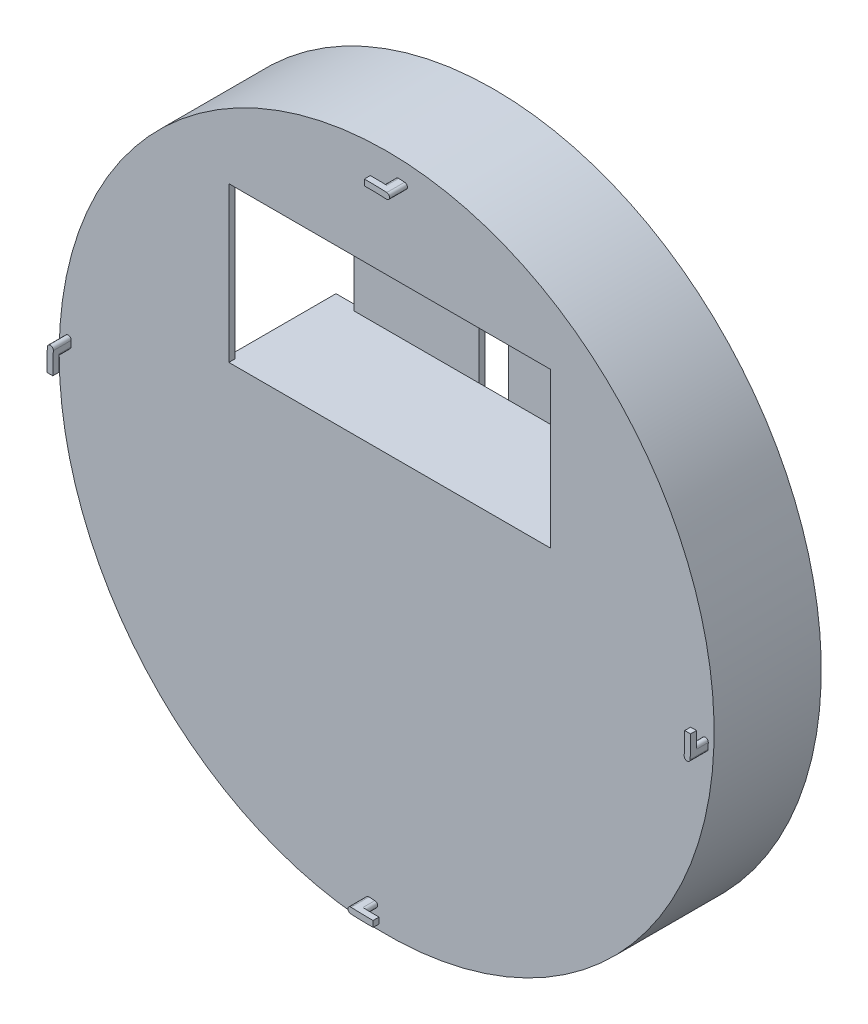
SolidWorks part; units mm, degrees
ref_plane "Plan de face" through (0, 0, 0) normal (0, 0, 1) x (1, 0, 0)
ref_plane "Plan de dessus" through (0, 0, 0) normal (0, 1, 0) x (1, 0, 0)
ref_plane "Plan de droite" through (0, 0, 0) normal (1, 0, 0) x (0, 0, -1)
sketch "Esquisse1" plane through (0, 0, 0) normal (0, 0, 1) x (1, 0, 0)
  ellipse E0 centre (0, 0) end of major axis (0, 57) minor radius 55
  dimension "D1" = 55
  dimension "D2" = 57
extrude "Boss.-Extru.1" add sketch "Esquisse1" along normal blind 18
sketch "Esquisse2" plane through (0, 0, 0) normal (0, 0, -1) x (-1, 0, 0)
  circle A0 centre (0, 0) radius 50
  dimension "D1" = 100
extrude "Enlèv. mat.-Extru.1" cut sketch "Esquisse2" against normal blind 17
sketch "Esquisse3" plane through (0, 0, 17) normal (0, 0, -1) x (-1, 0, 0)
  line L1 (-28.5, 40) -> (27.5, 40)
  line L2 (-28.5, 40) -> (-28.5, 12)
  line L3 (-28.5, 12) -> (27.5, 12)
  line L4 (27.5, 40) -> (27.5, 12)
  line L5 (-28.5, 40) -> (27.5, 12) construction
  line L6 (-28.5, 12) -> (27.5, 40) construction
  circle A0 centre (0, 0) radius 50 construction
  circle A1 centre (0, 0) radius 50 construction
  point P0 (-0.5, 26)
  dimension "D3" = 40
  dimension "D4" = 27.5
  dimension "D1" = 56
  dimension "D2" = 28
extrude "Boss.-Extru.2" add sketch "Esquisse3" along normal blind 18
sketch "Esquisse4" plane through (0, 0, 18) normal (0, 0, 1) x (1, 0, 0)
  line L0 (10.45, 0) -> (-10.45, 0) construction
  line L1 (-26.5, 39) -> (27.5, 39)
  line L2 (-26.5, 39) -> (-26.5, 13)
  line L3 (-26.5, 13) -> (27.5, 13)
  line L4 (27.5, 39) -> (27.5, 13)
  line L5 (-26.5, 39) -> (27.5, 13) construction
  line L6 (-26.5, 13) -> (27.5, 39) construction
  line L7 (0, -10.45) -> (0, 10.45) construction
  point P0 (0.5, 26)
  dimension "D1" = 54
  dimension "D2" = 26
  dimension "D3" = 39
  dimension "D4" = 27.5
extrude "Enlèv. mat.-Extru.2" cut sketch "Esquisse4" against normal blind 18
sketch "Esquisse5" plane through (0, 0, -1) normal (0, 0, -1) x (-1, 0, 0)
  line L0 (-2.5, 12) -> (2.5, 12)
  line L1 (-2.5, 12) -> (-2.5, 40)
  line L2 (2.5, 12) -> (2.5, 40)
  line L3 (-2.5, 40) -> (2.5, 40)
  line L4 (-28.5, 12) -> (27.5, 12) construction
  line L5 (-28.5, 12) -> (27.5, 12) construction
  line L7 (0, 10.45) -> (0, -10.45) construction
  dimension "D1" = 5
  dimension "D2" = 2.5
  dimension "D3" = 28
extrude "Enlèv. mat.-Extru.3" cut sketch "Esquisse5" against normal blind 1
sketch "Esquisse7" plane through (2.5, 0, 0) normal (-1, 0, 0) x (0, 0, 1)
  line L0 (-1, 40) -> (-1, 12)
  line L1 (-1, 12) -> (3, 40)
  line L2 (3, 40) -> (-1, 40)
  dimension "D1" = 4
extrude "Enlèv. mat.-Extru.4" cut sketch "Esquisse7" along normal blind 5
sketch "Esquisse8" plane through (0, 0, 17) normal (0, 0, -1) x (-1, 0, 0)
  line L0 (0, 40) -> (0, 50) construction
  line L1 (2.5, 40) -> (-2.5, 40) construction
  line L2 (-5.5, 46) -> (5.5, 46) construction
  line L3 (27.5, 40) -> (-28.5, 40) construction
  line L8 (-5.5, 46) -> (-5.5, 40)
  line L9 (-5.5, 46) -> (-2, 46)
  line L10 (-2, 46) -> (-2, 45)
  line L11 (-2, 45) -> (-4.5, 45)
  line L12 (-4.5, 45) -> (-4.5, 41)
  line L13 (-4.5, 41) -> (-2, 41)
  line L14 (-2, 41) -> (-2, 40)
  line L15 (-2, 40) -> (-5.5, 40)
  line L16 (5.5, 46) -> (5.5, 40)
  line L17 (2, 40) -> (5.5, 40)
  line L18 (2, 41) -> (2, 40)
  line L19 (4.5, 41) -> (2, 41)
  line L20 (4.5, 45) -> (4.5, 41)
  line L21 (2, 45) -> (4.5, 45)
  line L22 (2, 46) -> (2, 45)
  line L23 (5.5, 46) -> (2, 46)
  circle A0 centre (0, 0) radius 50 construction
  point P10 (0, 46)
  dimension "D1" = 11
  dimension "D2" = 6
  dimension "D3" = 6
  dimension "D4" = 3.5
  dimension "D5" = 3.5
  dimension "D6" = 1
  dimension "D7" = 4
  dimension "D8" = 1
extrude "Boss.-Extru.3" add sketch "Esquisse8" along normal blind 10
sketch "Esquisse9" plane through (0, 0, -1) normal (0, 0, -1) x (-1, 0, 0)
  line L0 (27.5, 12) -> (27.5, 40) construction
  line L7 (27.5, 13) -> (27.5, 39)
  line L8 (27.5, 13) -> (23.5, 13)
  line L9 (27.5, 39) -> (23.5, 39)
  line L10 (23.5, 13) -> (23.5, 39)
  point P0 (27.5, 26)
  dimension "D3" = 4
  dimension "D4" = 26
extrude "Enlèv. mat.-Extru.5" cut sketch "Esquisse9" against normal blind 18
sketch "Esquisse10" plane through (0, 0, -1) normal (0, 0, -1) x (-1, 0, 0)
  line L0 (-5.5, 40) -> (-28.5, 40) construction
  line L1 (-2.5, 40) -> (-2.5, 12) construction
  line L2 (27.5, 40) -> (2.5, 40) construction
  line L3 (2.5, 12) -> (2.5, 40) construction
  circle A0 centre (-9.5, 26) radius 3
  circle A1 centre (9.5, 26) radius 3
  dimension "D1" = 14
  dimension "D2" = 7
  dimension "D3" = 14
  dimension "D4" = 7
  dimension "D5" = 6
  dimension "D6" = 6
extrude "Boss.-Extru.4" add sketch "Esquisse10" along normal blind 15
sketch "Esquisse11" plane through (0, 0, 18) normal (0, 0, 1) x (1, 0, 0)
  arc A0 (-53.521, 2) -> (-53.4743, 3) centre (0, 0) cw construction
  arc A1 (-53.9735, 3.028) -> (-54.0207, 2.0187) centre (0, 0) ccw
  arc A2 (-52.9751, 2.972) -> (-53.0214, 1.9813) centre (0, 0) ccw
  arc A3 (-52.9751, 2.972) -> (-53.9735, 3.028) centre (-53.4743, 3) ccw
  arc A4 (-54.0207, 2.0187) -> (-53.0214, 1.9813) centre (-53.521, 2) ccw
  arc A5 (2, 53.521) -> (3, 53.4743) centre (0, 0) cw construction
  arc A6 (3.028, 53.9735) -> (2.0187, 54.0207) centre (0, 0) ccw
  arc A7 (2.972, 52.9751) -> (1.9813, 53.0214) centre (0, 0) ccw
  arc A8 (2.972, 52.9751) -> (3.028, 53.9735) centre (3, 53.4743) ccw
  arc A9 (2.0187, 54.0207) -> (1.9813, 53.0214) centre (2, 53.521) ccw
  arc A10 (53.521, -2) -> (53.4743, -3) centre (0, 0) cw construction
  arc A11 (53.9735, -3.028) -> (54.0207, -2.0187) centre (0, 0) ccw
  arc A12 (52.9751, -2.972) -> (53.0214, -1.9813) centre (0, 0) ccw
  arc A13 (52.9751, -2.972) -> (53.9735, -3.028) centre (53.4743, -3) ccw
  arc A14 (54.0207, -2.0187) -> (53.0214, -1.9813) centre (53.521, -2) ccw
  arc A15 (-2, -53.521) -> (-3, -53.4743) centre (0, 0) cw construction
  arc A16 (-3.028, -53.9735) -> (-2.0187, -54.0207) centre (0, 0) ccw
  arc A17 (-2.972, -52.9751) -> (-1.9813, -53.0214) centre (0, 0) ccw
  arc A18 (-2.972, -52.9751) -> (-3.028, -53.9735) centre (-3, -53.4743) ccw
  arc A19 (-2.0187, -54.0207) -> (-1.9813, -53.0214) centre (-2, -53.521) ccw
  point P4 (-53.5, 2.5001)
  point P14 (2.5001, 53.5)
  point P21 (53.5, -2.5001)
  point P28 (-2.5001, -53.5)
  point P33 (0, 0)
  dimension "D1" = 53.5
  dimension "D2" = 0.5
  dimension "D3" = 1
  dimension "D4" = 3
  dimension "D5" = 4
extrude "Boss.-Extru.5" add sketch "Esquisse11" along normal blind 3
ref_plane "Plan1" through (0, 0, 0) normal (0.056, 0.9984, 0) x (0.9984, -0.056, 0)
sketch "Esquisse12" plane through (0, 0, 0) normal (0.056, 0.9984, 0) x (0.9984, -0.056, 0)
  line L0 (-54.0584, -21) -> (-53.0584, -21)
  line L1 (-54.0584, -21) -> (-54.0584, -20)
  line L2 (-53.0584, -21) -> (-53.0584, -20)
  line L3 (-54.0584, -20) -> (-53.0584, -20)
  dimension "D1" = 1
revolve "Révolution1" add sketch "Esquisse12" angle 4 about axis through (0, 0, 17) along (0, 0, -1) reverse direction yes
pattern_circular "Répétition circulaire1" count 4 every 90 about axis through (0, 0, 17) along (0, 0, -1) of "Révolution1"
